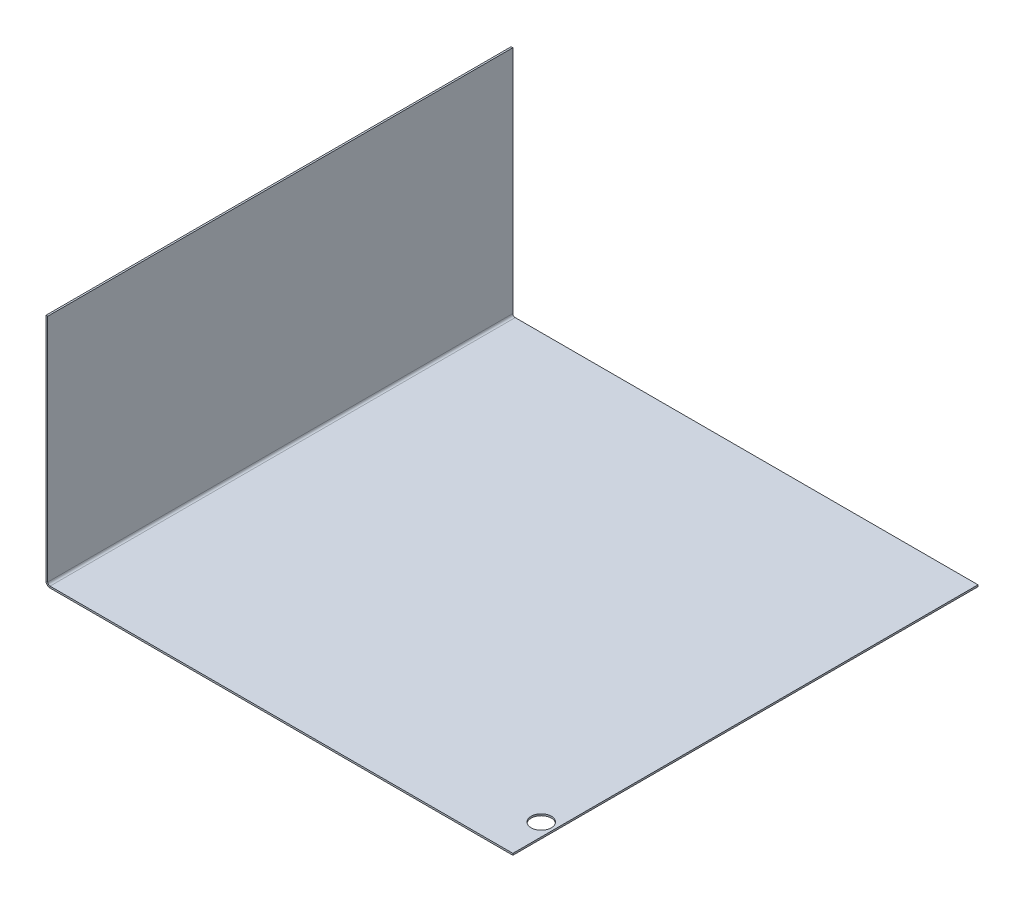
SolidWorks part; units mm, degrees
note: '?' marks a value the reader was unsure of. The reader was unsure of these and kept them because the rebuilt part matched: bend radius of "BaseBend1".
ref_plane "Front Plane" through (0, 0, 0) normal (0, 0, 1) x (1, 0, 0)
ref_plane "Top Plane" through (0, 0, 0) normal (0, 1, 0) x (1, 0, 0)
ref_plane "Right Plane" through (0, 0, 0) normal (1, 0, 0) x (0, 0, -1)
ref_axis "X AXIS" through (-88.99, 0, 0) along (1, 0, 0)?
ref_axis "Y AXIS" through (0, 55, 0) along (0, -1, 0)?
ref_axis "Z AXIS" through (0, 0, -88.99) along (0, 0, 1)?
sketch "Sketch1" plane through (0, 0, 0) normal (0, 0, 1) x (1, 0, 0)
  line L0 (0, 100) -> (0, 0)
  line L1 (0, 0) -> (200, 0)
  dimension "D1" = 100
  dimension "D2" = 200
base flange "Base-Flange1" sketch "Sketch1" end condition mid plane depth 200 reverse direction no thickness 0.7366 reverse thickness direction no bend radius 1
bend "BaseBend1" bend radius 1 bend angle 90 parameters "D5"=1
sketch "Sketch6" plane through (0, 0, 0) normal (0, 1, 0) x (1, 0, 0)
  circle A0 centre (194.4453, -82.2169) radius 4.3343
extrude "Cut-Extrude1" cut sketch "Sketch6" against normal blind 10
sketch "Bend-Lines1" plane through (0, 0, 0) normal (0, 1, 0) x (1, 0, 0)
sketch "Bounding-Box1" plane through (0, 0, 0) normal (0, 1, 0) x (1, 0, 0)
sheet metal parameters "Sheet-Metal2" thickness 0.7366 parameters "D1"=1
flat pattern "Flat-Pattern2" [suppressed]
sketch "Bend-Lines2" plane through (0, 0, 0) normal (0, 1, 0) x (1, 0, 0)
sketch "Bounding-Box2" [suppressed] plane through (0, 0, 0) normal (0, 1, 0) x (1, 0, 0)
bend of the flat pattern "Flatten-<BaseBend1>1"
sheet metal parameters "Sheet-Metal3" thickness 0.7366 parameters "D1"=1
flat pattern "Flat-Pattern2" [suppressed]
sketch "Bend-Lines2" plane through (0, 0, 0) normal (0, 1, 0) x (1, 0, 0)
sketch "Bounding-Box2" [suppressed] plane through (0, 0, 0) normal (0, 1, 0) x (1, 0, 0)
bend of the flat pattern "Flatten-<BaseBend1>1"
